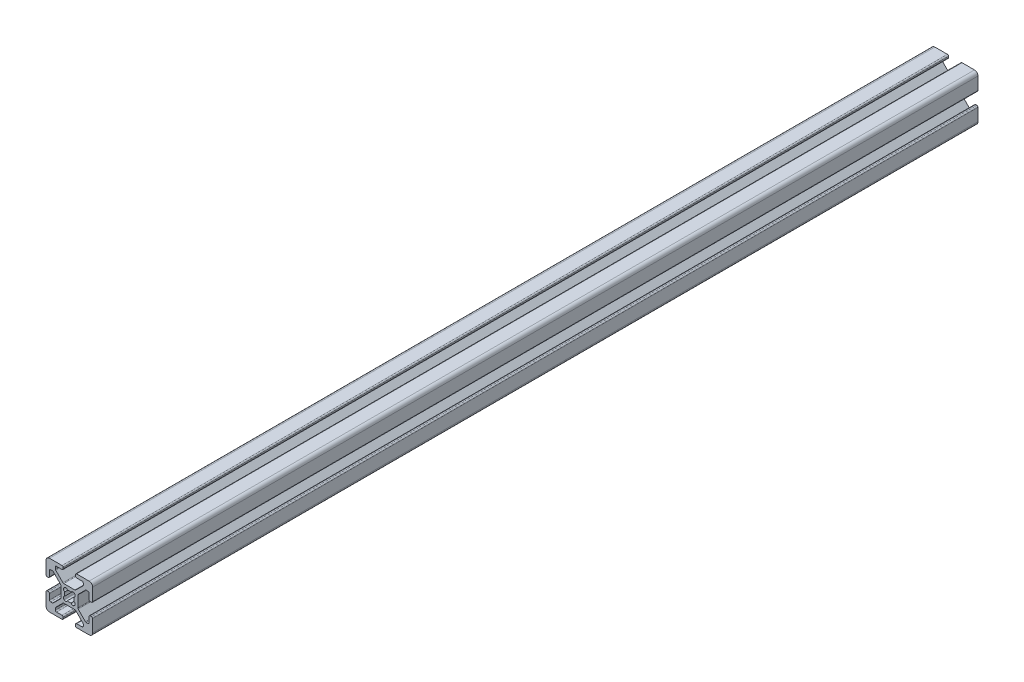
SolidWorks part; units mm, degrees
ref_plane "Front Plane" through (0, 0, 0) normal (0, 0, 1) x (1, 0, 0)
ref_plane "Top Plane" through (0, 0, 0) normal (0, 1, 0) x (1, 0, 0)
ref_plane "Right Plane" through (0, 0, 0) normal (1, 0, 0) x (0, 0, -1)
sketch "Sketch1" plane through (0, 0, 0) normal (0, 0, 1) x (1, 0, 0)
  line L0 (-5.0323, -0.3411) -> (-5.5163, -0.3411)
  line L1 (-6.0243, 0.1669) -> (-6.0243, 2.5159)
  line L2 (-4.5243, 0.1669) -> (-4.5243, 5.5289)
  line L3 (-10.8693, -5.355) -> (-10.8693, -0.5871)
  line L4 (-7.2582, 3.0239) -> (-6.5323, 3.0239)
  line L5 (-7.6174, 2.8752) -> (-10.7205, -0.2279)
  line L6 (-5.0323, -5.6011) -> (-5.5163, -5.6011)
  line L7 (-4.5243, -6.1091) -> (-4.5243, -11.4711)
  line L8 (-6.0243, -6.1091) -> (-6.0243, -8.4581)
  line L9 (-7.2582, -8.9661) -> (-6.5323, -8.9661)
  line L10 (-7.6174, -8.8173) -> (-10.7205, -5.7142)
  line L11 (-12.3994, -5.2756) -> (-12.2198, -5.096)
  line L12 (-17.1543, 6.5209) -> (-17.1543, 6.0369)
  line L13 (-17.6623, 7.0289) -> (-23.0243, 7.0289)
  line L14 (-17.6623, 5.5289) -> (-20.0113, 5.5289)
  line L15 (-12.1404, 0.6839) -> (-16.9082, 0.6839)
  line L16 (-20.5193, 4.295) -> (-20.5193, 5.0209)
  line L17 (-20.3705, 3.9358) -> (-17.2674, 0.8327)
  line L18 (-11.8943, 6.5209) -> (-11.8943, 6.0369)
  line L19 (-11.3863, 7.0289) -> (-6.0243, 7.0289)
  line L20 (-11.3863, 5.5289) -> (-9.0373, 5.5289)
  line L21 (-8.5293, 4.295) -> (-8.5293, 5.0209)
  line L22 (-8.6781, 3.9358) -> (-11.7812, 0.8327)
  line L23 (-12.2198, -0.8462) -> (-12.3994, -0.6666)
  line L24 (-24.0163, -5.6011) -> (-23.5323, -5.6011)
  line L25 (-24.5243, -6.1091) -> (-24.5243, -11.4711)
  line L26 (-23.0243, -6.1091) -> (-23.0243, -8.4581)
  line L27 (-18.1793, -0.5871) -> (-18.1793, -5.355)
  line L28 (-21.7904, -8.9661) -> (-22.5163, -8.9661)
  line L29 (-21.4312, -8.8173) -> (-18.3281, -5.7142)
  line L30 (-24.0163, -0.3411) -> (-23.5323, -0.3411)
  line L31 (-24.5243, 0.1669) -> (-24.5243, 5.5289)
  line L32 (-23.0243, 0.1669) -> (-23.0243, 2.5159)
  line L33 (-21.7904, 3.0239) -> (-22.5163, 3.0239)
  line L34 (-21.4312, 2.8752) -> (-18.3281, -0.2279)
  line L35 (-16.6492, -0.6666) -> (-16.8288, -0.8462)
  line L36 (-11.8943, -12.4631) -> (-11.8943, -11.9791)
  line L37 (-11.3863, -12.9711) -> (-6.0243, -12.9711)
  line L38 (-11.3863, -11.4711) -> (-9.0373, -11.4711)
  line L39 (-16.9082, -6.6261) -> (-12.1404, -6.6261)
  line L40 (-8.5293, -10.2371) -> (-8.5293, -10.9631)
  line L41 (-8.6781, -9.8779) -> (-11.7812, -6.7748)
  line L42 (-17.1543, -12.4631) -> (-17.1543, -11.9791)
  line L43 (-17.6623, -12.9711) -> (-23.0243, -12.9711)
  line L44 (-17.6623, -11.4711) -> (-20.0113, -11.4711)
  line L45 (-20.5193, -10.2371) -> (-20.5193, -10.9631)
  line L46 (-20.3705, -9.8779) -> (-17.2674, -6.7748)
  line L47 (-16.8288, -5.096) -> (-16.6492, -5.2756)
  arc A0 (-15.3283, -4.9062) -> (-13.7203, -4.9062) centre (-14.5243, -2.9711) ccw
  arc A1 (-6.0243, 2.5159) -> (-6.5323, 3.0239) centre (-6.5323, 2.5159) ccw
  arc A2 (-7.2582, 3.0239) -> (-7.6174, 2.8752) centre (-7.2582, 2.5159) ccw
  arc A3 (-10.7205, -0.2279) -> (-10.8693, -0.5871) centre (-10.3613, -0.5871) ccw
  arc A4 (-10.8693, -5.355) -> (-10.7205, -5.7142) centre (-10.3613, -5.355) ccw
  arc A5 (-7.6174, -8.8173) -> (-7.2582, -8.9661) centre (-7.2582, -8.4581) ccw
  arc A6 (-6.5323, -8.9661) -> (-6.0243, -8.4581) centre (-6.5323, -8.4581) ccw
  arc A7 (-5.5163, -5.6011) -> (-6.0243, -6.1091) centre (-5.5163, -6.1091) ccw
  arc A8 (-4.5243, -6.1091) -> (-5.0323, -5.6011) centre (-5.0323, -6.1091) ccw
  arc A9 (-5.0323, -0.3411) -> (-4.5243, 0.1669) centre (-5.0323, 0.1669) ccw
  arc A10 (-6.0243, 0.1669) -> (-5.5163, -0.3411) centre (-5.5163, 0.1669) ccw
  arc A11 (-13.7203, -4.9062) -> (-12.3994, -5.2756) centre (-12.9559, -4.7191) ccw
  arc A12 (-12.2198, -5.096) -> (-12.5892, -3.775) centre (-12.7763, -4.5395) ccw
  arc A13 (-17.1543, 6.5209) -> (-17.6623, 7.0289) centre (-17.6623, 6.5209) ccw
  arc A14 (-17.6623, 5.5289) -> (-17.1543, 6.0369) centre (-17.6623, 6.0369) ccw
  arc A15 (-12.5892, -3.775) -> (-12.5892, -2.1671) centre (-14.5243, -2.9711) ccw
  arc A16 (-17.2674, 0.8327) -> (-16.9082, 0.6839) centre (-16.9082, 1.1919) ccw
  arc A17 (-20.0113, 5.5289) -> (-20.5193, 5.0209) centre (-20.0113, 5.0209) ccw
  arc A18 (-20.5193, 4.295) -> (-20.3705, 3.9358) centre (-20.0113, 4.295) ccw
  arc A19 (-11.8943, 6.0369) -> (-11.3863, 5.5289) centre (-11.3863, 6.0369) ccw
  arc A20 (-11.3863, 7.0289) -> (-11.8943, 6.5209) centre (-11.3863, 6.5209) ccw
  arc A21 (-8.5293, 5.0209) -> (-9.0373, 5.5289) centre (-9.0373, 5.0209) ccw
  arc A22 (-8.6781, 3.9358) -> (-8.5293, 4.295) centre (-9.0373, 4.295) ccw
  arc A23 (-12.1404, 0.6839) -> (-11.7812, 0.8327) centre (-12.1404, 1.1919) ccw
  arc A24 (-12.5892, -2.1671) -> (-12.2198, -0.8462) centre (-12.7763, -1.4027) ccw
  arc A25 (-12.3994, -0.6666) -> (-13.7203, -1.0359) centre (-12.9559, -1.223) ccw
  arc A26 (-24.0163, -5.6011) -> (-24.5243, -6.1091) centre (-24.0163, -6.1091) ccw
  arc A27 (-23.0243, -6.1091) -> (-23.5323, -5.6011) centre (-23.5323, -6.1091) ccw
  arc A28 (-13.7203, -1.0359) -> (-15.3283, -1.0359) centre (-14.5243, -2.9711) ccw
  arc A29 (-18.3281, -5.7142) -> (-18.1793, -5.355) centre (-18.6873, -5.355) ccw
  arc A30 (-23.0243, -8.4581) -> (-22.5163, -8.9661) centre (-22.5163, -8.4581) ccw
  arc A31 (-21.7904, -8.9661) -> (-21.4312, -8.8173) centre (-21.7904, -8.4581) ccw
  arc A32 (-23.5323, -0.3411) -> (-23.0243, 0.1669) centre (-23.5323, 0.1669) ccw
  arc A33 (-24.5243, 0.1669) -> (-24.0163, -0.3411) centre (-24.0163, 0.1669) ccw
  arc A34 (-22.5163, 3.0239) -> (-23.0243, 2.5159) centre (-22.5163, 2.5159) ccw
  arc A35 (-21.4312, 2.8752) -> (-21.7904, 3.0239) centre (-21.7904, 2.5159) ccw
  arc A36 (-18.1793, -0.5871) -> (-18.3281, -0.2279) centre (-18.6873, -0.5871) ccw
  arc A37 (-15.3283, -1.0359) -> (-16.6492, -0.6666) centre (-16.0927, -1.223) ccw
  arc A38 (-16.8288, -0.8462) -> (-16.4594, -2.1671) centre (-16.2723, -1.4027) ccw
  arc A39 (-11.8943, -12.4631) -> (-11.3863, -12.9711) centre (-11.3863, -12.4631) ccw
  arc A40 (-11.3863, -11.4711) -> (-11.8943, -11.9791) centre (-11.3863, -11.9791) ccw
  arc A41 (-16.4594, -2.1671) -> (-16.4594, -3.775) centre (-14.5243, -2.9711) ccw
  arc A42 (-11.7812, -6.7748) -> (-12.1404, -6.6261) centre (-12.1404, -7.1341) ccw
  arc A43 (-9.0373, -11.4711) -> (-8.5293, -10.9631) centre (-9.0373, -10.9631) ccw
  arc A44 (-8.5293, -10.2371) -> (-8.6781, -9.8779) centre (-9.0373, -10.2371) ccw
  arc A45 (-17.1543, -11.9791) -> (-17.6623, -11.4711) centre (-17.6623, -11.9791) ccw
  arc A46 (-17.6623, -12.9711) -> (-17.1543, -12.4631) centre (-17.6623, -12.4631) ccw
  arc A47 (-20.5193, -10.9631) -> (-20.0113, -11.4711) centre (-20.0113, -10.9631) ccw
  arc A48 (-20.3705, -9.8779) -> (-20.5193, -10.2371) centre (-20.0113, -10.2371) ccw
  arc A49 (-16.9082, -6.6261) -> (-17.2674, -6.7748) centre (-16.9082, -7.1341) ccw
  arc A50 (-16.4594, -3.775) -> (-16.8288, -5.096) centre (-16.2723, -4.5395) ccw
  arc A51 (-16.6492, -5.2756) -> (-15.3283, -4.9062) centre (-16.0927, -4.7191) ccw
  arc A52 (-4.5243, 5.5289) -> (-6.0243, 7.0289) centre (-6.0243, 5.5289) ccw
  arc A53 (-6.0243, -12.9711) -> (-4.5243, -11.4711) centre (-6.0243, -11.4711) ccw
  arc A54 (-24.5243, -11.4711) -> (-23.0243, -12.9711) centre (-23.0243, -11.4711) ccw
  arc A55 (-23.0243, 7.0289) -> (-24.5243, 5.5289) centre (-23.0243, 5.5289) ccw
extrude "Extrude1" add sketch "Sketch1" along normal blind 330 and the other way blind 50
